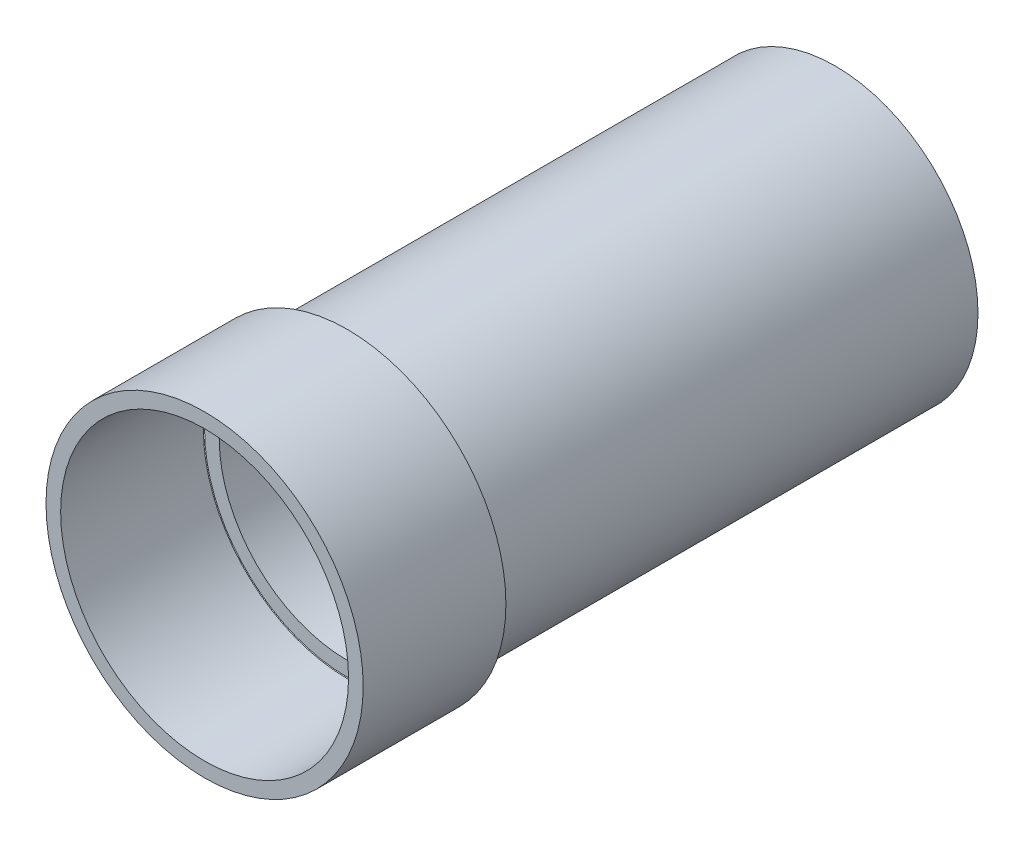
SolidWorks part; units mm, degrees
ref_plane "Front Plane" through (0, 0, 0) normal (0, 0, 1) x (1, 0, 0)
ref_plane "Top Plane" through (0, 0, 0) normal (0, 1, 0) x (1, 0, 0)
ref_plane "Right Plane" through (0, 0, 0) normal (1, 0, 0) x (0, 0, -1)
ref_plane "Plane2" through (0, 0, 40) normal (0, 0, 1) x (1, 0, 0)
sketch "Sketch1" plane through (0, 0, 0) normal (0, 0, 1) x (1, 0, 0)
  circle A0 centre (0, 0) radius 21
  circle A1 centre (0, 0) radius 23.4
  dimension "D1" = 42
  dimension "D2" = 2.4
extrude "Boss-Extrude1" add sketch "Sketch1" along normal blind 80
ref_plane "Plane1" through (42.6, 0, 0) normal (1, 0, 0) x (0, 0, -1)
sketch "Sketch2" plane through (42.6, 0, 0) normal (1, 0, 0) x (0, 0, -1)
  line L0 (-80, -23.4) -> (0, -23.4) construction
  line L1 (-55, 68.4) -> (-55, 38.4)
  line L2 (-55, 38.4) -> (-25, 38.4)
  line L3 (-25, 68.4) -> (-25, 38.4)
  line L5 (-52.4071, 47.3459) -> (-54.64, 65.4771) construction
  line L6 (-27.7048, 47.3599) -> (-25.3755, 65.479) construction
  line L8 (-55, 68.4) -> (-25, 68.4)
  circle A1 centre (-40, -53.4) radius 4.25
  circle A2 centre (-39.0222, -61.34) radius 1.6
  circle A3 centre (-40.4019, -45.4101) radius 1.6
  circle A4 centre (-39.4388, -43.9166) radius 1.6
  circle A5 centre (-42.8453, -44.3361) radius 1.6
  point P20 (-30.8186, -52.6048)
  dimension "D1" = 8
  dimension "D3" = 8.5
  dimension "D4" = 30
  dimension "D5" = 3.2
  dimension "D8" = 3.2
  dimension "D2" = 30
  dimension "D6" = 8
  dimension "D9" = 9.5
  dimension "D10" = 30
  dimension "D7" = 2
extrude "Boss-Extrude2" add sketch "Sketch2" along normal blind 2.4 separate body rebuild error yes
sketch "Sketch9" plane through (0, 0, 80) normal (0, 0, 1) x (1, 0, 0)
  circle A0 centre (0, 0) radius 23.6
  circle A1 centre (0, 0) radius 26
  dimension "D1" = 47.2
  dimension "D2" = 52
extrude "Boss-Extrude6" add sketch "Sketch9" along normal blind 23.4 separate body
sketch "Sketch10" plane through (0, 0, 80) normal (0, 0, 1) x (1, 0, 0)
  circle A0 centre (0, 0) radius 21
  circle A1 centre (0, 0) radius 26
ref_plane "Plane3" through (0, 24, 0) normal (0, 1, 0) x (1, 0, 0)
